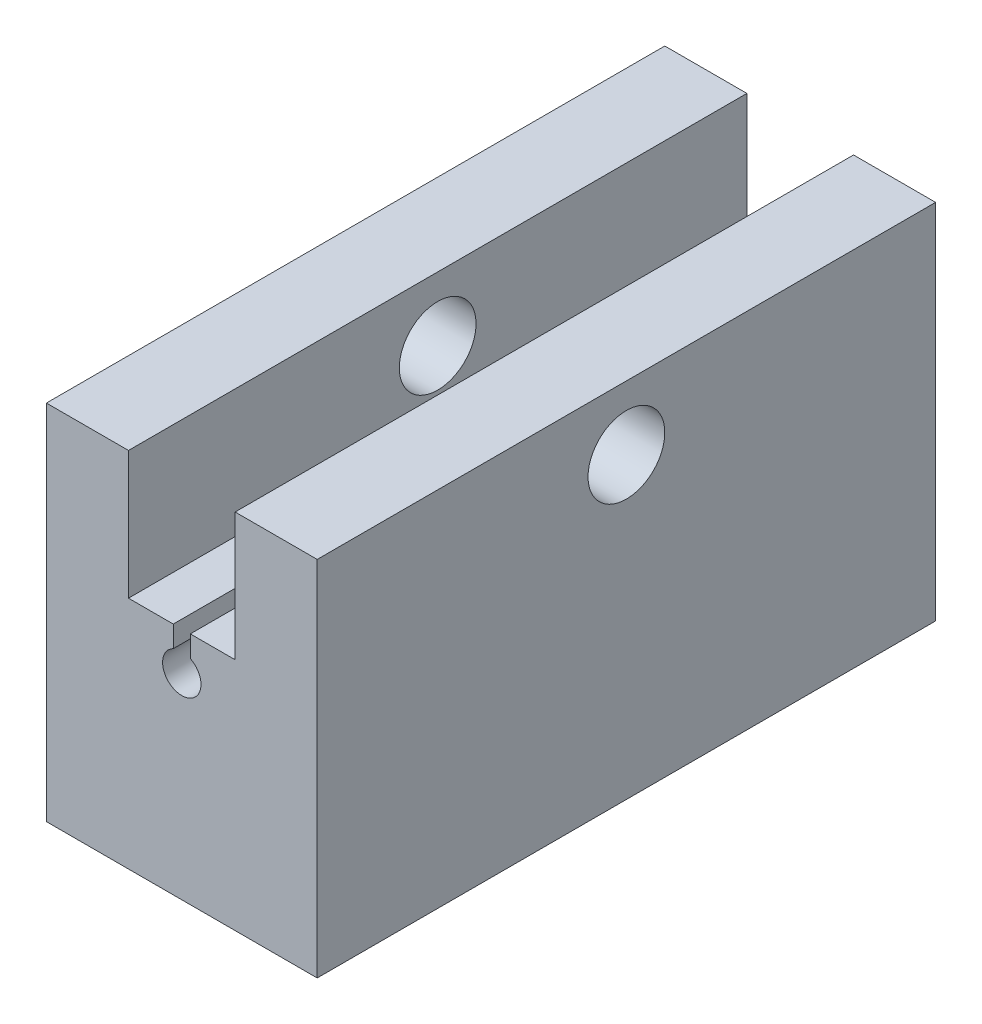
SolidWorks part; units mm, degrees
ref_plane "Front Plane" through (0, 0, 0) normal (0, 0, 1) x (1, 0, 0)
ref_plane "Top Plane" through (0, 0, 0) normal (0, 1, 0) x (1, 0, 0)
ref_plane "Right Plane" through (0, 0, 0) normal (1, 0, 0) x (0, 0, -1)
sketch "Sketch1" plane through (0, 0, 0) normal (0, 1, 0) x (1, 0, 0)
  line L1 (-6.35, -14.5) -> (6.35, -14.5)
  line L2 (-6.35, -14.5) -> (-6.35, 14.5)
  line L3 (-6.35, 14.5) -> (6.35, 14.5)
  line L4 (6.35, -14.5) -> (6.35, 14.5)
  line L5 (-6.35, -14.5) -> (6.35, 14.5) construction
  line L6 (-6.35, 14.5) -> (6.35, -14.5) construction
  point P0 (0, 0)
  dimension "D1" = 12.7
  dimension "D2" = 29
extrude "Boss-Extrude1" add sketch "Sketch1" along normal blind 7
hole_wizard "Hole1" positions "Sketch2" profile "Sketch3" legacy end condition through all
sketch "Sketch2" plane through (0, 0, 0) normal (0, -1, 0) x (-1, 0, 0)
  line L0 (0, -7.5) -> (0, 7.5) construction
  point P0 (0, -7.5)
  point P2 (0, 7.5)
  point P13 (0, 0)
  dimension "D1" = 15
sketch "Sketch3" plane through (0, 0, 7.5) normal (1, 0, 0) x (0, 0, -1)
  line L0 (0, 0) -> (0, 7)
  line L1 (0, 7) -> (2.8, 7)
  line L2 (2.8, 7) -> (2.8, 6)
  line L3 (2.8, 6) -> (3, 6)
  line L4 (3, 6) -> (3, 0)
  line L5 (3, 0) -> (0, 0)
  line L6 (0, 110) -> (0, -10) construction
  dimension "Diameter" = 5.6
  dimension "Depth" = 7
  dimension "C-Bore Diameter" = 6
  dimension "C-Bore Depth" = 6
sketch "Sketch4" plane through (-6.35, 0, 0) normal (-1, 0, 0) x (0, 0, 1)
  line L1 (-14.5, 7) -> (14.5, 7)
  line L2 (-14.5, 7) -> (-14.5, 17)
  line L3 (-14.5, 17) -> (14.5, 17)
  line L4 (14.5, 7) -> (14.5, 17)
  dimension "D1" = 10
extrude "Boss-Extrude2" add sketch "Sketch4" against normal up to surface (12.7 mm away) up to face at (6.35, 3.5, 0)
sketch "Sketch5" plane through (0, 0, -14.5) normal (0, 0, -1) x (-1, 0, 0)
  line L0 (-0.4, 11) -> (-0.4, 10)
  line L1 (-6.35, 6.9975) -> (6.35, 6.9975) construction
  line L3 (0.4, 11) -> (0.4, 10)
  line L4 (-0.4, 11) -> (-2.5, 11)
  line L5 (-2.5, 11) -> (-2.5, 17)
  line L6 (-6.35, 17) -> (6.35, 17) construction
  line L7 (-2.5, 17) -> (2.5, 17)
  line L8 (2.5, 17) -> (2.5, 11)
  line L9 (2.5, 11) -> (0.4, 11)
  line L10 (-6.35, 17) -> (-6.35, 0) construction
  line L11 (6.35, 17) -> (6.35, 0) construction
  arc A0 (-0.4, 10) -> (0.4, 10) centre (0, 9.1938) ccw
  point P12 (2.5, 14)
  point P13 (0, 17)
  dimension "D1" = 0.9
  dimension "D2" = 0.8
  dimension "D3" = 1
  dimension "D4" = 5
  dimension "D5" = 6
  dimension "D6" = 10.0025
extrude "Cut-Extrude1" cut sketch "Sketch5" against normal through all
hole_wizard "M3 Clearance Hole1" positions "Sketch6" profile "Sketch8" hole size "M3" standard "ANSI Metric" end condition through all
sketch "Sketch6" plane through (-6.35, 0, 0) normal (-1, 0, 0) x (0, 0, 1)
  line L0 (14.5, 17) -> (-14.5, 17) construction
  point P0 (0, 14)
  dimension "D1" = 3
sketch "Sketch8" plane through (-6.35, 14, 0) normal (0, 1, 0) x (0, 0, 1)
  line L0 (0, 0) -> (0, 12.7)
  line L1 (0, 12.7) -> (1.8, 12.7)
  line L2 (1.8, 12.7) -> (1.8, 0)
  line L5 (1.8, 0) -> (0, 0)
  line L11 (0, -6.35) -> (0, 107.95) construction
  dimension "Thru Hole Dia." = 3.6
  dimension "Thru Hole Depth" = 12.7
chamfer "Chamfer1" distance 6 distance2 0.2 2 edges at (0, 6, -10.5) (0, 6, 4.5) first distance on face at (0, 6, -10.5) first distance on face at (0, 6, 4.5)
